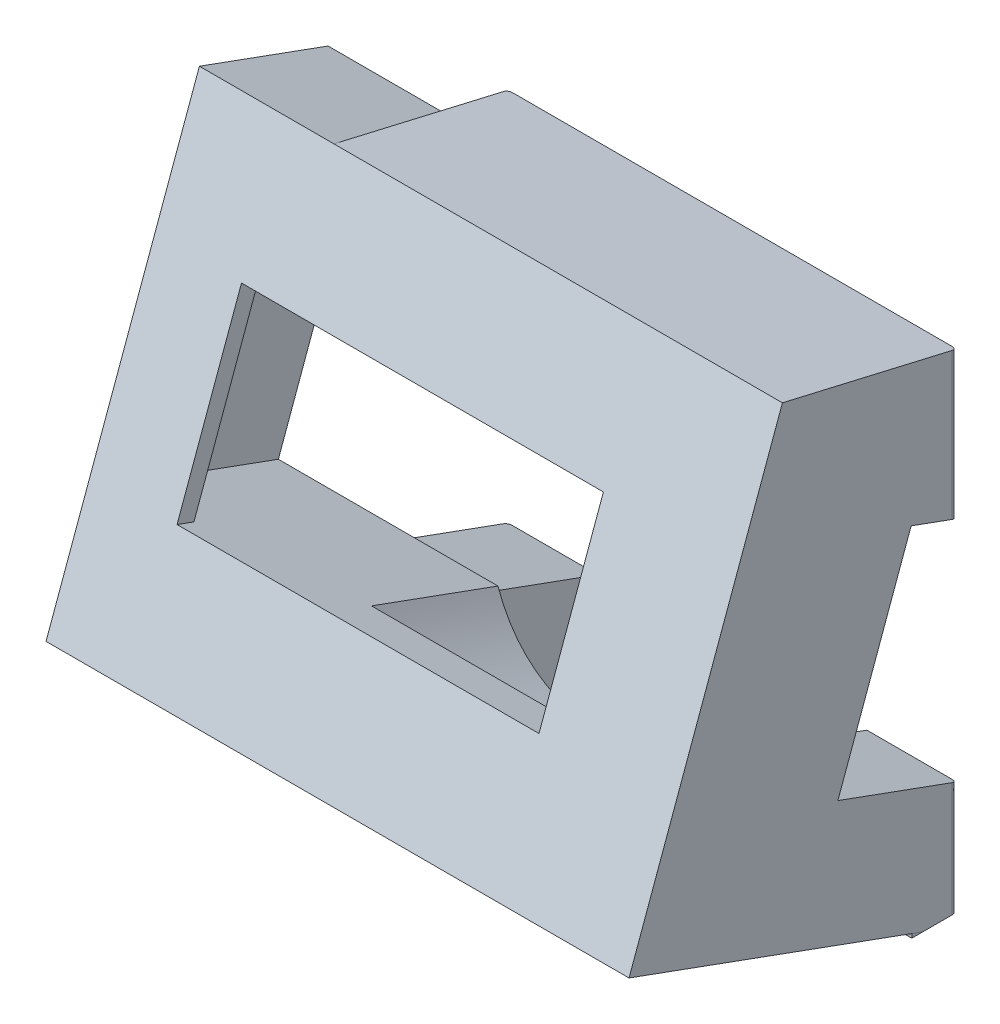
SolidWorks part; units mm, degrees
ref_plane "Front Plane" through (0, 0, 0) normal (0, 0, 1) x (1, 0, 0)
ref_plane "Top Plane" through (0, 0, 0) normal (0, 1, 0) x (1, 0, 0)
ref_plane "Right Plane" through (0, 0, 0) normal (1, 0, 0) x (0, 0, -1)
sketch "Sketch2" plane through (0, 0, 0) normal (0, 0, 1) x (1, 0, 0)
  line L0 (-100, -75) -> (-100, -45)
  line L1 (-100, 75) -> (100, 75)
  line L2 (-100, 75) -> (-100, -75)
  line L3 (-100, -75) -> (100, -75)
  line L4 (100, 75) -> (100, -75)
  line L5 (-100, 75) -> (100, -75) construction
  line L6 (-100, -75) -> (100, 75) construction
  line L7 (-100, -45) -> (-60, -45)
  line L8 (-60, -45) -> (-60, -75)
  line L9 (100, -75) -> (100, -45)
  line L10 (100, -45) -> (60, -45)
  line L11 (60, -45) -> (60, -75)
  line L12 (-60, -75) -> (-60, -65)
  line L13 (-60, -65) -> (60, -65)
  line L14 (-60, -45) -> (-50, -45)
  line L15 (-50, -45) -> (-50, -55)
  line L16 (-50, -55) -> (-60, -55)
  line L17 (60, -45) -> (50, -45)
  line L18 (50, -45) -> (50, -55)
  line L19 (50, -55) -> (60, -55)
  line L20 (-55, -55) -> (-55, -50)
  line L21 (-55, -50) -> (-50, -50)
  line L22 (-50, -45) -> (-52, -45)
  line L23 (-50, -45) -> (-50, -47)
  line L24 (0, -65) -> (0, -61.3332)
  line L25 (-58, -53) -> (-52, -53)
  line L26 (-58, -53) -> (-58, -47)
  line L27 (-58, -47) -> (-52, -47)
  line L28 (-52, -53) -> (-52, -47)
  line L29 (-58, -53) -> (-52, -47) construction
  line L30 (-58, -47) -> (-52, -53) construction
  line L31 (58, -47) -> (52, -47)
  line L32 (52, -53) -> (52, -47)
  line L33 (58, -53) -> (52, -53)
  line L34 (58, -53) -> (58, -47)
  point P0 (0, 0)
  dimension "D1" = 200
  dimension "D2" = 150
  dimension "D3" = 40
extrude "Boss-Extrude1" add sketch "Sketch2" along normal blind 5 contours L19 L18 L17 L10 L4 L1 L2 L7 L14 L15 L16 L8 L13 L11 | L18 L19 L11 L17 L34 L33 L32 L31 | L28 L21 L15 L14 L8 L16 L20 L25 L26 L27 | L28 L25 L20 L16 L15 L21 region at (0, 9.084, 0) region at (-56, -45.1414, 0) region at (-51.9375, -53.0625, 0) region at (55, -54.8586, 0)
sketch "Sketch3" plane through (0, 0, 5) normal (0, 0, 1) x (1, 0, 0)
  line L0 (-100, 75) -> (-100, -45) construction
  line L1 (-100, 75) -> (-100, 55)
  line L2 (-100, 55) -> (100, 55)
  line L3 (100, 75) -> (100, -45) construction
  line L4 (100, 55) -> (100, 75)
  line L5 (100, 75) -> (-100, 75)
extrude "Cut-Extrude1" cut sketch "Sketch3" against normal blind 5
sketch "Sketch4" plane through (0, 0, 0) normal (0, 0, -1) x (-1, 0, 0)
  line L0 (-100, 55) -> (100, 55)
  line L1 (100, 55) -> (100, -45)
  line L2 (100, -45) -> (-100, -45)
  line L3 (-100, -45) -> (-100, 55)
  line L4 (100, 55) -> (95, 55)
  line L5 (95, 55) -> (95, -45)
  line L6 (95, -45) -> (100, -45)
  line L7 (100, 55) -> (100, 45)
  line L8 (100, 45) -> (95, 45)
  line L9 (95, 45) -> (95, 50)
  line L10 (95, 50) -> (100, 50)
  line L11 (100, 50) -> (99, 50)
  line L12 (100, 50) -> (100, 49)
  line L13 (97.5, 45) -> (97.5, 47.5)
  line L14 (100, 5) -> (95, 5)
  line L15 (96, 46) -> (99, 46)
  line L16 (96, 46) -> (96, 49)
  line L17 (96, 49) -> (99, 49)
  line L18 (99, 46) -> (99, 49)
  line L19 (96, 46) -> (99, 49) construction
  line L20 (96, 49) -> (99, 46) construction
  line L21 (96, -39) -> (99, -39)
  line L22 (99, -36) -> (99, -39)
  line L23 (96, -36) -> (99, -36)
  line L24 (96, -36) -> (96, -39)
  line L25 (100, 5) -> (100, 7.5)
  line L26 (100, 5) -> (100, 2.5)
  line L27 (100, 2.5) -> (95, 2.5)
  line L28 (95, 2.5) -> (95, 7.5)
  line L29 (95, 7.5) -> (100, 7.5)
  line L30 (100, 2.5) -> (99, 2.5)
  line L31 (100, 2.5) -> (100, 3.5)
  line L32 (0, -45) -> (0, -36)
  line L33 (96, 6.5) -> (99, 6.5)
  line L34 (96, 6.5) -> (96, 3.5)
  line L35 (96, 3.5) -> (99, 3.5)
  line L36 (99, 6.5) -> (99, 3.5)
  line L37 (96, 6.5) -> (99, 3.5) construction
  line L38 (96, 3.5) -> (99, 6.5) construction
  line L39 (97.5, -36) -> (97.5, -39)
  line L40 (100, 50) -> (95, 50)
  line L41 (100, 50) -> (100, 45)
  line L42 (100, 45) -> (95, 45)
  line L43 (95, 50) -> (95, 45)
  line L44 (100, 50) -> (95, 45) construction
  line L45 (100, 45) -> (95, 50) construction
  line L46 (97.5, -39) -> (97.5, -40)
  line L47 (-100, 45) -> (-95, 45)
  line L48 (100, -35) -> (95, -35)
  line L49 (100, -35) -> (100, -40)
  line L50 (100, -40) -> (95, -40)
  line L51 (95, -35) -> (95, -40)
  line L52 (100, -35) -> (95, -40) construction
  line L53 (100, -40) -> (95, -35) construction
  line L54 (-95, 50) -> (-95, 45)
  line L55 (-100, 50) -> (-95, 50)
  line L56 (-100, 50) -> (-100, 45)
  line L57 (-100, 5) -> (-100, 7.5)
  line L58 (-95, 7.5) -> (-100, 7.5)
  line L59 (-95, 2.5) -> (-95, 7.5)
  line L60 (-100, 2.5) -> (-95, 2.5)
  line L61 (-100, 5) -> (-100, 2.5)
  line L62 (-100, -40) -> (-95, -40)
  line L63 (-95, -35) -> (-95, -40)
  line L64 (-100, -35) -> (-95, -35)
  line L65 (-100, -35) -> (-100, -40)
  point P31 (97.5, 5)
  point P44 (97.5, -37.5)
  line M38 (-100, 55) -> (-100, -45)
extrude "Cut-Extrude2" cut sketch "Sketch4" against normal blind 5 contours L55 L3 L47 L54 | L3 L60 L59 L58 M38 | L64 L3 L62 L63 | L18 L15 L8 L1 L7 L10 L5 L16 L17 | L15 L18 L17 L16 | L33 L36 L14 L1 L29 L5 L34 | L14 L36 L35 L34 L5 L27 L1 L26 | L36 L14 L34 L35 | L36 L33 L34 L14 | L50 L1 L48 L5 L21 L24 L23 L22 | L23 L39 L21 L22 | L39 L23 L24 L21 region at (97.5, 47.5, 0) region at (-96.75, 46.0424, 0) region at (-97, 49.9293, 0) region at (97.5, 5, 0) region at (-97.5, 6.5313, 0) region at (-97.5, 3.4688, 0) region at (-97.5, 5.75, 0) region at (-97.5, 4.25, 0) region at (97.5, -37.5, 0) region at (-96.75, -37.5, 0) region at (-98.25, -37.5, 0) region at (-97.5, -35.0707, 0)
sketch "Sketch6" plane through (0, 0, 0) normal (0, 0, -1) x (-1, 0, 0)
  line L0 (0, -65) -> (0, -45)
  line L1 (60, -65) -> (-60, -65) construction
  line L2 (0, -45) -> (50, -45)
  line L3 (50, -45) -> (50, -65)
  line L4 (0, -45) -> (-50, -45)
  line L5 (-50, -45) -> (-50, -65)
  line L6 (-50, -45) -> (-60, -45)
  line M21 (-60, -65) -> (60, -65)
extrude "Boss-Extrude2" add sketch "Sketch6" along normal blind 100 contours L3 L2 L0 M21 | L4 L5 L0 M21 region at (25, -55, 0) region at (-25, -55, 0)
sketch "Sketch8" plane through (50, 0, 0) normal (1, 0, 0) x (0, 0, -1)
  line L0 (100, -45) -> (100, 55)
  line L1 (100, 55) -> (78.5761, 55)
  line L2 (100, -45) -> (42.1791, -45)
  line L3 (100, -45) -> (0, -45) construction
  line L4 (78.5761, 55) -> (42.1791, -45)
  line L5 (60.3776, 5) -> (63.7978, 14.3969)
  line L6 (60.3776, 5) -> (56.9574, -4.3969)
  line M8 (100, -45) -> (0, -45)
  dimension "D1" = 21.4239
  dimension "D2" = 57.8209
extrude "Boss-Extrude3" add sketch "Sketch8" against normal blind 100 contours L1 L4 L0 M8 region at (50, -2.655, -78.7957)
sketch "Sketch12" plane through (50, 0, 0) normal (1, 0, 0) x (0, 0, -1)
  line L0 (42.1791, -45) -> (78.5761, 55)
  line L2 (42.1791, -45) -> (100, -45)
  line L3 (100, 55) -> (100, -65) construction
  line L4 (100, -45) -> (100, 55)
  line L5 (78.5761, 55) -> (83.897, 55)
  line L6 (100, 55) -> (78.5761, 55) construction
  line L7 (83.897, 55) -> (88.897, 55)
  line L8 (83.897, 55) -> (47.5, -45)
  line L9 (88.897, 55) -> (52.5, -45)
  line M5 (100, 55) -> (78.5761, 55)
  line M6 (78.5761, 55) -> (42.1791, -45)
  dimension "D1" = 5.3209
extrude "Cut-Extrude4" cut sketch "Sketch12" against normal blind 100 contours L8 L2 M5 M6 region at (50, 5, -63.0381)
sketch "Sketch13" plane through (0, -20.5302, -56.4063) normal (0, 0.342, 0.9397) x (1, 0, 0)
  line L0 (-50, 80.3776) -> (50, 80.3776)
  line L1 (50, 80.3776) -> (50, -26.0402)
  line L2 (50, -26.0402) -> (-50, -26.0402)
  line L3 (-50, -26.0402) -> (-50, 80.3776)
  line L4 (0, 80.3776) -> (0, 27.1687)
  circle A0 centre (0, 27.1687) radius 10
extrude "Boss-Extrude5" add sketch "Sketch13" along normal blind 100 contours A0 region at (6.8711, 11.4567, -68.0486)
sketch "Sketch14" plane through (0, 13.6718, 37.563) normal (0, 0.342, 0.9397) x (1, 0, 0)
  circle A0 centre (0, 27.1687) radius 10.3
  circle A1 centre (0, 27.1687) radius 12.5
  circle M3 centre (0, 27.1687) radius 10
  dimension "D1" = 25
extrude "Cut-Extrude5" cut sketch "Sketch14" against normal blind 100 contours M3 | A1 M3 | A0 M3 | A0 | A1 region at (-10.0087, 39.202, 28.2708) region at (-12.1464, 39.202, 28.2708) region at (0, 39.202, 28.2708)
ref_plane "Plane1" through (0, 13.6718, 37.563) normal (0, 0.342, 0.9397) x (1, 0, 0)
sketch "Sketch15" plane through (0, 13.6718, 37.563) normal (0, 0.342, 0.9397) x (1, 0, 0)
  circle A0 centre (0, 27.1687) radius 10
  circle A1 centre (0, 27.1687) radius 12.5
  circle A2 centre (0, 27.1687) radius 15
ref_plane "Plane2" through (0, 0, -30) normal (0, 0, -1) x (-1, 0, 0)
extrude "Boss-Extrude6" add sketch "Sketch15" against normal blind 40 contours A2 A1 region at (-14.5757, 39.202, 28.2708)
sketch "Sketch16" plane through (0, 0, -30) normal (0, 0, -1) x (-1, 0, 0)
  line L0 (0, 61.0723) -> (0, 0)
  line L1 (0, 0) -> (25, 0)
  line L2 (25, 0) -> (25, 61.0723)
  line L3 (25, 61.0723) -> (-25, 61.0723)
  line L4 (-25, 61.0723) -> (-25, 0)
  line L5 (-25, 0) -> (0, 0)
sketch "Sketch17" plane through (0, 13.6718, 37.563) normal (0, 0.342, 0.9397) x (1, 0, 0)
  circle A0 centre (0, 27.1687) radius 10.3
  circle A1 centre (0, 27.1687) radius 12.5
extrude "Cut-Extrude10" cut sketch "Sketch16" against normal blind 35 contours L4 L5 L0 L3 | L2 L3 L0 L1 region at (-12.5, 30.5361, -30) region at (12.5, 30.5361, -30)
sketch "Sketch18" plane through (0, 0, 5) normal (0, 0, 1) x (1, 0, 0)
  line L0 (25, 55) -> (25, 0)
  line L1 (25, 0) -> (-25, 0)
  line L2 (-25, 0) -> (-25, 55)
  line L3 (-25, 55) -> (25, 55)
  line L4 (-30, 55) -> (-30, 60)
  line L5 (30, 0) -> (30, 55)
  line L6 (25, 55) -> (100, 55) construction
  line L7 (30, 55) -> (25, 55)
  line L8 (30, 0) -> (30, -5)
  line L9 (30, -5) -> (-30, -5)
  line L10 (-30, -5) -> (-30, 55)
  line L11 (-100, 55) -> (-25, 55) construction
  line L12 (-30, 55) -> (-25, 55)
  line L13 (-30, 60) -> (30, 60)
  line L14 (30, 60) -> (30, 55)
  line L15 (-30, 55) -> (30, 55)
  line M5 (25, 55) -> (25, 0)
  line M6 (25, 0) -> (-25, 0)
  line M7 (-25, 0) -> (-25, 55)
  line M8 (-25, 55) -> (-100, 55)
  line M40 (100, 55) -> (25, 55)
sketch "Sketch20" plane through (0, 0, 5) normal (0, 0, -1) x (-1, 0, 0)
  ellipse E2 centre (0, 30.7322) end of major axis (0, 44.0344) minor radius 12.5 (0, 44.0344) -> (0, 44.0344) ccw
  ellipse E3 centre (0, 30.7322) end of major axis (0, 44.0344) minor radius 12.5
  ellipse E5 centre (0, 30.7322) end of major axis (0, 46.6948) minor radius 15 (0, 46.6948) -> (0, 46.6948) ccw
  ellipse E6 centre (0, 30.7322) end of major axis (0, 46.6948) minor radius 15
  point P0 (0, 0)
  dimension "D1" = 0
  dimension "D2" = 0
sketch "Sketch21" plane through (0, 0, -30) normal (0, 0, -1) x (-1, 0, 0)
  line L0 (0, 30.7322) -> (0, 46.6948)
  line L1 (0, 46.6948) -> (-15, 46.6948)
  line L2 (-15, 46.6948) -> (-15, 14.7695)
  line L3 (-15, 14.7695) -> (15, 14.7695)
  line L4 (15, 14.7695) -> (15, 46.6948)
  line L5 (15, 46.6948) -> (0, 46.6948)
  line L6 (-25, 55) -> (-25, 0)
  line L7 (-25, 0) -> (25, 0)
  line L8 (25, 0) -> (25, 55)
  line L9 (25, 55) -> (-25, 55)
  line L10 (-30, 55) -> (-30, 60)
  line L11 (-30, 60) -> (-25, 60)
  line L12 (-25, 60) -> (30, 60)
  line L13 (30, 60) -> (30, 55)
  line L14 (30, 55) -> (30, -5)
  line L15 (30, -5) -> (-30, -5)
  line L16 (-30, -5) -> (-30, 55)
  line L17 (-25, 55) -> (-30, 55)
  line L18 (25, 55) -> (30, 55)
  line L19 (-25, 55) -> (25, 55)
  ellipse E2 centre (0, 30.7322) end of major axis (0, 46.6948) minor radius 15
  ellipse E3 centre (0, 30.7322) end of major axis (0, 46.6948) minor radius 15
  ellipse E5 centre (0, 30.7322) end of major axis (0, 44.0344) minor radius 12.5
  ellipse E6 centre (0, 30.7322) end of major axis (0, 44.0344) minor radius 12.5
  dimension "D1" = 0
  dimension "D2" = 0
extrude "Cut-Extrude11" cut sketch "Sketch15<4>" against normal blind 15 contours A2 A1 region at (-14.5757, 39.202, 28.2708)
sketch "Sketch15<4>" plane through (0, 13.6718, 37.563) normal (0, 0.342, 0.9397) x (1, 0, 0) same geometry as "Sketch15"
sketch "Sketch22" plane through (0, 0, 0) normal (0, 0, -1) x (-1, 0, 0)
  line L0 (30, -5) -> (-30, -5)
  line L1 (-30, -5) -> (-30, 60)
  line L2 (-30, 60) -> (30, 60)
  line L3 (30, 60) -> (30, -5)
  line L4 (25, 0) -> (-25, 0)
  line L5 (-25, 0) -> (-25, 55)
  line L6 (-25, 55) -> (25, 55)
  line L7 (25, 55) -> (25, 0)
  line L8 (-25, 55) -> (-30, 55)
  line L9 (-25, 55) -> (-100, 55) construction
  line L10 (25, 55) -> (30, 55)
  line L11 (30, -5) -> (30, 55) construction
  line L12 (25, 0) -> (30, 0)
  line L13 (-25, 0) -> (-30, 0)
  line M17 (25, 0) -> (-25, 0)
  line M18 (-25, 0) -> (-25, 55)
  line M56 (25, 55) -> (25, 0)
extrude "Boss-Extrude7" add sketch "Sketch18" along normal blind 5 contours L10 L9 L8 L5 M40 M5 M6 M7 M8 region at (27.5, 54.1515, 5)
sketch "Sketch23" plane through (0, 8.5415, 23.4676) normal (0, 0.342, 0.9397) x (1, 0, 0)
  circle A0 centre (0, 27.1687) radius 15
  circle A1 centre (0, 27.1687) radius 10.3
  circle A2 centre (0, 27.1687) radius 12.5
  circle M4 centre (0, 27.1687) radius 12.5
  circle M5 centre (0, 27.1687) radius 15
extrude "Boss-Extrude8" add sketch "Sketch23" against normal blind 25 contours M5 M4 region at (-14.5757, 34.0717, 14.1754)
extrude "Cut-Extrude12" cut sketch "Sketch21" against normal blind 35 contours E6 E3 | E6 | L8 L9 L6 L7 L5 L4 L3 L2 L1 | E3 L4 L5 | E3 L1 L2 | E3 L2 L3 | E3 L3 L4 region at (-10.4462, 41.5478, -30) region at (11.6495, 43.1293, -30) region at (-11.6495, 43.1293, -30) region at (0, 17.795, -30) region at (11.6495, 18.335, -30) region at (-11.6495, 18.335, -30) region at (0, 54.2567, -30)
extrude "Boss-Extrude9" add sketch "Sketch22" against normal blind 5 contours L6 M18 M17 M56 region at (0, 27.5, 0)
extrude "Cut-Extrude13" cut sketch "Sketch23<3>" against normal blind 20 contours A1 M4 | A1 region at (0, 34.0717, 14.1754) region at (-12.1464, 34.0717, 14.1754)
sketch "Sketch23<3>" plane through (0, 8.5415, 23.4676) normal (0, 0.342, 0.9397) x (1, 0, 0) same geometry as "Sketch23"
sketch "Sketch27" plane through (0, 8.5415, 23.4676) normal (0, 0.342, 0.9397) x (1, 0, 0)
  line L1 (-2, 42.1687) -> (2, 42.1687)
  line L2 (-2, 42.1687) -> (-2, 12.1687)
  line L3 (-2, 12.1687) -> (2, 12.1687)
  line L4 (2, 42.1687) -> (2, 12.1687)
  line L5 (-2, 42.1687) -> (2, 12.1687) construction
  line L6 (-2, 12.1687) -> (2, 42.1687) construction
  line L7 (-15, 29.1687) -> (15, 29.1687)
  line L8 (-15, 29.1687) -> (-15, 25.1687)
  line L9 (-15, 25.1687) -> (15, 25.1687)
  line L10 (15, 29.1687) -> (15, 25.1687)
  line L11 (-15, 29.1687) -> (15, 25.1687) construction
  line L12 (-15, 25.1687) -> (15, 29.1687) construction
  circle A0 centre (0, 27.1687) radius 12.5
  circle A1 centre (0, 27.1687) radius 15
  point P0 (0, 27.1687)
  point P6 (0, 27.1687)
  circle M8 centre (0, 27.1687) radius 12.5
  circle M9 centre (0, 27.1687) radius 15
  dimension "D1" = 4
  dimension "D2" = 4
  dimension "D3" = 30
  dimension "D4" = 30
extrude "Cut-Extrude15" cut sketch "Sketch27" against normal blind 3 contours L4 L2 M9 M8 | L9 L7 M8 M9 | L9 L7 M9 M8 | L4 L2 M8 M9 region at (0, 46.9463, 9.4894) region at (-13.7008, 34.0717, 14.1754) region at (13.7008, 34.0717, 14.1754) region at (0, 21.1972, 18.8613)
sketch "Sketch28" plane through (0, 0, 10) normal (0, 0, 1) x (1, 0, 0)
  line L0 (-25, 55) -> (-25, 5)
  line L1 (-25, 55) -> (-25, 0) construction
  line L2 (-25, 5) -> (25, 5)
  line L3 (25, 55) -> (25, 0) construction
  line L4 (25, 5) -> (25, 0)
  line L5 (25, 0) -> (-25, 0)
  line L6 (-25, 0) -> (-25, 5)
  line L7 (-25, 0) -> (-30, 0)
  line L8 (-30, -5) -> (-30, 55) construction
  line L9 (-30, 0) -> (-30, -5)
  line L10 (-30, -5) -> (30, -5)
  line L11 (30, -5) -> (30, 0)
  line L12 (30, 55) -> (30, -5) construction
  line L13 (30, 0) -> (25, 0)
  line M1 (-30, 55) -> (-30, -5)
  line M2 (-30, -5) -> (30, -5)
  line M3 (30, -5) -> (30, 55)
  line M5 (25, 55) -> (25, 0)
  line M6 (25, 0) -> (-25, 0)
  line M7 (-25, 0) -> (-25, 55)
extrude "Cut-Extrude16" cut sketch "Sketch28" against normal blind 5 contours L13 L7 M3 M6 M1 M2 region at (0, -2.5, 10)
extrude "Boss-Extrude12" add sketch "Sketch28<3>" against normal blind 5 contours L2 M7 M6 M5 region at (0, 2.5, 10)
sketch "Sketch28<3>" plane through (0, 0, 10) normal (0, 0, 1) x (1, 0, 0) same geometry as "Sketch28"
sketch "Sketch31" plane through (0, 8.5415, 23.4676) normal (0, 0.342, 0.9397) x (1, 0, 0)
  line L0 (0, 33.5187) -> (6.35, 33.5187)
  line L1 (6.35, 33.5187) -> (6.35, 27.1687)
  line L2 (6.35, 27.1687) -> (6.35, 20.8187)
  line L3 (6.35, 20.8187) -> (0, 20.8187)
  line L4 (6.35, 33.5187) -> (-17.65, 33.5187)
  line L5 (-17.65, 33.5187) -> (-17.65, 20.8187)
  line L6 (-17.65, 20.8187) -> (6.35, 20.8187)
  line L7 (-17.65, 33.5187) -> (-22.85, 33.5187)
  line L8 (-22.85, 33.5187) -> (-22.85, 20.8187)
  line L9 (-22.85, 20.8187) -> (-17.65, 20.8187)
  line L10 (6.35, 33.5187) -> (11.55, 33.5187)
  line L11 (11.55, 33.5187) -> (11.55, 20.8187)
  line L12 (11.55, 20.8187) -> (6.35, 20.8187)
  line L14 (-25, 52.1687) -> (25, 52.1687)
  line L15 (-25, 52.1687) -> (-25, 2.1687)
  line L16 (-25, 2.1687) -> (25, 2.1687)
  line L17 (25, 52.1687) -> (25, 2.1687)
  line L18 (-25, 52.1687) -> (25, 2.1687) construction
  line L19 (-25, 2.1687) -> (25, 52.1687) construction
  circle A0 centre (0, 27.1687) radius 2.5
  circle A1 centre (0, 27.1687) radius 6.35
  arc M3 (14.8661, 29.1687) -> (2, 42.0347) centre (0, 27.1687) ccw
  line M4 (2, 42.0347) -> (2, 39.5076)
  arc M5 (2, 39.5076) -> (12.339, 29.1687) centre (0, 27.1687) cw
  line M6 (12.339, 29.1687) -> (14.8661, 29.1687)
  dimension "D1" = 5
  dimension "D2" = 6.35
  dimension "D3" = 50
  dimension "D4" = 50
extrude "Boss-Extrude13" add sketch "Sketch31" along normal blind 20 contours L17 L14 L15 L16 L11 L12 L3 L6 L9 L8 L7 L4 L0 L10 M5 M4 M3 M6 | L10 L11 M5 M6 M3 M4 | L12 L11 L10 L1 L2 M5 | L11 L10 M5 | L8 L9 L5 L7 region at (8.9293, 34.0232, 14.193) region at (-20.25, 34.0717, 14.1754) region at (9.074, 42.6669, 11.047) region at (11.2964, 39.562, 12.1771) region at (0, 56.8996, 5.8667)
sketch "Sketch32" plane through (0, 15.3819, 42.2614) normal (0, 0.342, 0.9397) x (1, 0, 0)
  line L0 (6.35, 33.5187) -> (11.55, 33.5187)
  line L1 (11.55, 33.5187) -> (11.55, 20.8222)
  line L2 (6.35, 20.8187) -> (11.55, 20.8222)
  line L3 (6.35, 27.1687) -> (6.35, 29.1687)
  line L4 (6.35, 33.5187) -> (6.35, 20.8187) construction
  line L5 (6.35, 29.1687) -> (9.35, 29.1687)
  line L6 (9.35, 29.1687) -> (9.35, 25.1687)
  line L7 (9.35, 25.1687) -> (6.35, 25.1687)
  line L8 (6.35, 25.1687) -> (6.35, 27.1687)
sketch "Sketch33" plane through (-25, 0, 0) normal (-1, 0, 0) x (0, 0, 1)
  line L0 (5.6249, 57.564) -> (24.4187, 64.4044)
  line L1 (24.4187, 64.4044) -> (41.5197, 17.4198)
  line L2 (41.5197, 17.4198) -> (22.7259, 10.5794)
  line L3 (22.7259, 10.5794) -> (5.6249, 57.564)
  line L4 (24.4187, 64.4044) -> (0, 64.4044)
  line L5 (0, 64.4044) -> (0, 55)
  line L6 (0, 64.4044) -> (-5, 64.4044)
  line L7 (-5, 64.4044) -> (-5, 55)
  line L8 (-5, 55) -> (6.5581, 55)
  line L9 (-5, 55) -> (-5, 45)
  line L10 (-5, 45) -> (0, 45)
  line L11 (0, 45) -> (0, 55)
  line L12 (5, 55) -> (5, 5.5)
  line L13 (5, 7.5) -> (5, 2.5) construction
  line L14 (5, 5.5) -> (41.5197, 5.5)
  line L15 (41.5197, 5.5) -> (41.5197, 17.4198)
  line L16 (5.6249, 57.564) -> (10.7552, 43.4686)
  line L17 (22.7259, 10.5794) -> (17.5956, 24.6748)
  line L18 (17.5956, 24.6748) -> (5, 20.0904)
  line L19 (5, 20.0904) -> (5, 5.5)
  line L20 (10.7552, 43.4686) -> (5, 41.3739)
sketch "Sketch34" plane through (0, 0, -100) normal (0, 0, -1) x (-1, 0, 0)
  line L0 (-100, 55) -> (100, 55)
  line L1 (100, 55) -> (100, -65)
  line L2 (100, -65) -> (-100, -65)
  line L3 (-100, -65) -> (-100, 55)
  line L4 (0, 55) -> (30, 55)
  line L5 (30, 55) -> (30, 5)
  line L6 (0, 55) -> (-30, 55)
  line L7 (-30, 55) -> (-30, 5)
  line L9 (30, 5) -> (30, 0)
  line L10 (30, 0) -> (25, 0)
  line L11 (-30, 0) -> (-30, 5)
  line L12 (-30, 55) -> (-25, 55)
  line L13 (-25, 55) -> (-25, 5)
  line L14 (30, 0) -> (25, 0)
  line L15 (25, 5) -> (25, 55)
  line L16 (-25, 0) -> (-30, 0)
  line L17 (30, 55) -> (25, 55)
  line L18 (-25, 0) -> (25, 0)
  line L19 (-30, 5) -> (30, 5)
  line M5 (50, -65) -> (50, 55)
  line M6 (50, 55) -> (-50, 55)
  line M7 (-50, 55) -> (-50, -65)
  line M8 (-50, -65) -> (50, -65)
extrude "Cut-Extrude19" cut sketch "Sketch34" against normal blind 105 contours L18 L16 L11 L7 L0 L5 L9 L10 M7 M8 M5 M6 | L2 L1 L0 M5 | L3 L2 L0 M7 | L13 L19 L15 L4 M6 region at (75, -5, -100) region at (0, -17.3276, -100) region at (0, 30, -100) region at (-75, -5, -100)
extrude "Cut-Extrude20" cut sketch "Sketch34<3>" against normal blind 110 contours L7 L19 L13 L6 | L19 L11 L16 L18 L10 L9 | L15 L19 L5 L0 region at (27.5, 30, -100) region at (0, 2.5, -100) region at (-27.5, 30, -100)
sketch "Sketch34<3>" plane through (0, 0, -100) normal (0, 0, -1) x (-1, 0, 0) same geometry as "Sketch34"
sketch "Sketch36" plane through (25, 0, 0) normal (1, 0, 0) x (0, 0, -1)
  line L0 (-24.4187, 64.4044) -> (-5.6249, 57.564)
  line L1 (-5.6249, 57.564) -> (-22.7259, 10.5794)
  line L2 (-22.7259, 10.5794) -> (-41.5197, 17.4198)
  line L3 (-41.5197, 17.4198) -> (-24.4187, 64.4044)
  line L4 (-24.4187, 64.4044) -> (5, 57.564)
  line L6 (5, 57.564) -> (5, 55)
  line L7 (5, 55) -> (0, 55)
  line L9 (5, 55) -> (5, 45)
  line L10 (5, 45) -> (0, 45)
  line L11 (0, 45) -> (0, 55)
  line L12 (-5, 55) -> (0, 55)
  line L13 (-5, 55) -> (-6.5581, 55)
  line L14 (-5, 55) -> (-5, 41.3739)
  line L15 (-5, 41.3739) -> (-10.7552, 43.4686)
  line L16 (-5, 41.3739) -> (-5, 20.0904)
  line L17 (-5, 20.0904) -> (-5, 5.5)
  line L18 (-5, 5.5) -> (-8.7703, 5.5)
  line L20 (-5, 20.0904) -> (-5, 41.3739)
  line L21 (-5, 20.0904) -> (-17.5956, 24.6748)
  line L22 (-22.7259, 10.5794) -> (-8.7703, 5.5)
  line M6 (-22.7259, 10.5794) -> (-5.6249, 57.564)
  line M7 (-5.6249, 57.564) -> (-24.4187, 64.4044)
ref_plane "Plane3" through (0, 1.7011, 4.6737) normal (0, -0.342, -0.9397) x (-1, 0, 0)
sketch "Sketch38" plane through (0, 1.7011, 4.6737) normal (0, -0.342, -0.9397) x (-1, 0, 0)
  circle A2 centre (0, 27.1687) radius 15
  circle A3 centre (0, 27.1687) radius 15
  circle A5 centre (0, 27.1687) radius 12.5
  circle A6 centre (0, 27.1687) radius 12.5
  dimension "D1" = 0
  dimension "D2" = 0
extrude "Cut-Extrude21" cut sketch "Sketch38" against normal blind 20
extrude "Boss-Extrude15" add sketch "Sketch36" against normal blind 50 contours L13 L12 L7 L6 L4 L1 M7 | L11 L10 L9 L7 | L15 L14 L13 L1 | L22 L18 L17 L21 M6 region at (25, 58.2724, 4.924) region at (25, 47.4608, 7.0152) region at (25, 14.5458, 12.7218) region at (25, 50, -2.5)
sketch "Sketch42" plane through (0, 2.0379, -0.7417) normal (0, -0.9397, 0.342) x (1, 0, 0)
  line L0 (-15, 24.9737) -> (15, 24.9737)
  line L1 (15, 24.9737) -> (-15, 24.9737) construction
  line L2 (15, 24.9737) -> (15, 6.5796)
  line L3 (-25, 6.5796) -> (25, 6.5796) construction
  line L4 (15, 6.5796) -> (-15, 6.5796)
  line L5 (-15, 6.5796) -> (-15, 24.9737)
extrude "Cut-Extrude24" cut sketch "Sketch42" against normal blind 55
sketch "Sketch43" plane through (-25, 0, 0) normal (-1, 0, 0) x (0, 0, 1)
  line L0 (5, 55) -> (5, 64.4044)
  line L1 (24.4187, 64.4044) -> (0, 64.4044) construction
  line L2 (5, 64.4044) -> (-5, 64.4044)
  line L3 (-5, 64.4044) -> (-5, 45)
  line L4 (-5, 45) -> (5, 45)
  line L5 (5, 46.6948) -> (5, 14.7695) construction
  line L6 (5, 45) -> (5, 55)
extrude "Cut-Extrude25" cut sketch "Sketch43" against normal blind 55
sketch "Sketch44" plane through (0, 0, 5) normal (0, 0, -1) x (-1, 0, 0)
  line L12 (-25, 64.4044) -> (25, 64.4044)
fillet "Fillet1" radius 0.5 4 edges at (-25, 50.6316, 5) (-25, 12.7952, 5) (25, 12.7952, 5) (25, 50.6316, 5)
sketch "Sketch45" plane through (-25, 0, 0) normal (-1, 0, 0) x (0, 0, 1)
  line L0 (5, 5.5) -> (10, 5.5)
  line L1 (5, 5.5) -> (41.5197, 5.5) construction
  line L2 (10, 5.5) -> (10, 5.9476)
  line L3 (41.5197, 17.4198) -> (8.7703, 5.5) construction
  line L4 (10, 5.9476) -> (8.7703, 5.5)
  line M11 (8.7703, 5.5) -> (41.5197, 17.4198)
extrude "Boss-Extrude16" add sketch "Sketch45" against normal blind 10 contours L0 L2 M11 region at (-25, 5.6492, 9.5901)
sketch "Sketch46" plane through (25, 0, 0) normal (1, 0, 0) x (0, 0, -1)
  line L0 (-5, 5.5) -> (-10, 5.5)
  line L1 (-10, 5.5) -> (-10, 5.9476)
  line L2 (-10, 5.9476) -> (-8.7703, 5.5)
  line M9 (-41.5197, 17.4198) -> (-8.7703, 5.5)
extrude "Boss-Extrude17" add sketch "Sketch46" against normal blind 10 separate body contours L1 L0 M9 region at (25, 5.6492, 9.5901)
sketch "Sketch47" plane through (0, 8.5415, 23.4676) normal (0, -0.342, -0.9397) x (-1, 0, 0)
  line L0 (0, 37.6687) -> (30.35, 37.6687)
  line L1 (0, 27.1687) -> (0, 37.6687)
  line L2 (0, 37.6687) -> (-10, 37.6687)
  line L3 (0, 27.1687) -> (0, 16.6687)
  line L4 (0, 16.6687) -> (-10, 16.6687)
  line L5 (-10, 16.6687) -> (-10, 37.6687)
  line L6 (-10, 37.6687) -> (0, 37.6687)
  line L7 (30.35, 37.6687) -> (30.35, 16.6687)
  line L8 (30.35, 16.6687) -> (0, 16.6687)
  line L9 (30.35, 37.6687) -> (37.85, 37.6687)
  line L10 (37.85, 37.6687) -> (37.85, 16.6687)
  line L11 (37.85, 16.6687) -> (30.35, 16.6687)
  line L12 (0, 37.6687) -> (-10, 37.6687)
  line L13 (-10, 16.6687) -> (-17.5, 16.6687)
  line L14 (-17.5, 16.6687) -> (-17.5, 37.6687)
  line L15 (-17.5, 37.6687) -> (-10, 37.6687)
  circle A0 centre (0, 27.1687) radius 3
  circle A1 centre (0, 27.1687) radius 17
  line M6 (-6.35, 33.5187) -> (17.65, 33.5187)
  line M7 (17.65, 33.5187) -> (17.65, 20.8187)
  line M8 (17.65, 20.8187) -> (-6.35, 20.8187)
  line M9 (-6.35, 20.8187) -> (-6.35, 33.5187)
  line M10 (15, 37.1687) -> (15, 53.9956)
  line M12 (-15, 53.9956) -> (-15, 37.1687)
  line M13 (-15, 37.1687) -> (-25, 37.1687)
  line M15 (-25, 17.1687) -> (-15, 17.1687)
  line M16 (-15, 17.1687) -> (-15, 2.1687)
  line M18 (15, 2.1687) -> (15, 17.1687)
  line M19 (15, 17.1687) -> (25, 17.1687)
  line M20 (25, 17.1687) -> (25, 37.1687)
  line M21 (25, 37.1687) -> (15, 37.1687)
sketch "Sketch48" plane through (-25, 0, 0) normal (-1, 0, 0) x (0, 0, 1)
  line L0 (5, 41.3739) -> (10.7552, 43.4686)
  line L1 (10.7552, 43.4686) -> (10.0711, 45.348)
  line L2 (19.3057, 19.9763) -> (9.0451, 48.1671) construction
  line L3 (10.0711, 45.348) -> (5, 43.5023)
  line L4 (5, 44.0344) -> (5, 17.4299) construction
  line L5 (5, 43.5023) -> (5, 41.3739)
  line L6 (5, 20.0904) -> (5, 18.0904)
  line L7 (5, 18.0904) -> (18.2384, 22.9087)
  line L8 (18.4506, 22.3256) -> (9.9001, 45.8179) construction
  line L9 (18.2384, 22.9087) -> (17.5956, 24.6748)
  line L10 (17.5956, 24.6748) -> (5, 20.0904)
extrude "Cut-Extrude26" cut sketch "Sketch48" against normal blind 50
sketch "Sketch49" plane through (0, 15.3819, 42.2614) normal (0, 0.342, 0.9397) x (1, 0, 0)
  line L0 (-25, 52.1687) -> (-40, 52.1687)
  line L1 (-25, 2.1687) -> (-40, 2.1687)
  line L2 (-40, 2.1687) -> (-40, 52.1687)
  line L3 (-25, 52.1687) -> (-25, 2.1687)
extrude "Boss-Extrude18" add sketch "Sketch49" against normal blind 20
sketch "Sketch50" plane through (-40, 0, 0) normal (-1, 0, 0) x (0, 0, 1)
  line L0 (10.0711, 45.348) -> (10.0711, 59.1823)
  line L1 (5.6249, 57.564) -> (24.4187, 64.4044) construction
  line L2 (10.0711, 59.1823) -> (5.6249, 57.564)
  line L3 (5.6249, 57.564) -> (10.0711, 45.348)
extrude "Cut-Extrude27" cut sketch "Sketch50" against normal blind 15
extrude "Cut-Extrude28" cut sketch "Sketch47" against normal blind 18 contours A1 L15 L14 L13 M12 M13 M15 M16 | L15 L14 M13 M12 | L14 L13 M16 M15 | L15 A1 L13 L5 | L11 L10 L9 L7 region at (13.0199, 34.0717, 14.1754) region at (-34.1, 34.0717, 14.1754) region at (17.214, 34.0717, 14.1754) region at (16.25, 43.7036, 10.6697) region at (16.25, 24.4399, 17.6811)
extrude "Cut-Extrude29" cut sketch "Sketch47<4>" against normal blind 20 contours L5 L4 L3 L1 L2 M8 M9 M6 | A1 L0 L1 M6 | L8 A1 L3 M8 | A1 L8 L0 M18 M19 M20 M21 M10 M6 M7 M8 | L8 L7 L0 M10 M21 M20 M19 M18 region at (-7.3665, 41.9359, 11.313) region at (0.2326, 41.9886, 11.2938) region at (-20.645, 34.0717, 14.1754) region at (-27.0477, 34.0717, 14.1754) region at (-7.3665, 26.2076, 17.0377)
sketch "Sketch47<4>" plane through (0, 8.5415, 23.4676) normal (0, -0.342, -0.9397) x (-1, 0, 0) same geometry as "Sketch47"
extrude "Cut-Extrude30" cut sketch "Sketch47<5>" against normal blind 15 contours L0 A1 L15 L2 | L13 A1 L8 L4 region at (0, 46.4267, 9.6785) region at (0, 21.7167, 18.6722)
sketch "Sketch47<5>" plane through (0, 8.5415, 23.4676) normal (0, -0.342, -0.9397) x (-1, 0, 0) same geometry as "Sketch47"
ref_plane "Plane4" through (-30.35, 50.7789, 29.378) normal (1, 0, 0) x (0, 0, -1)
